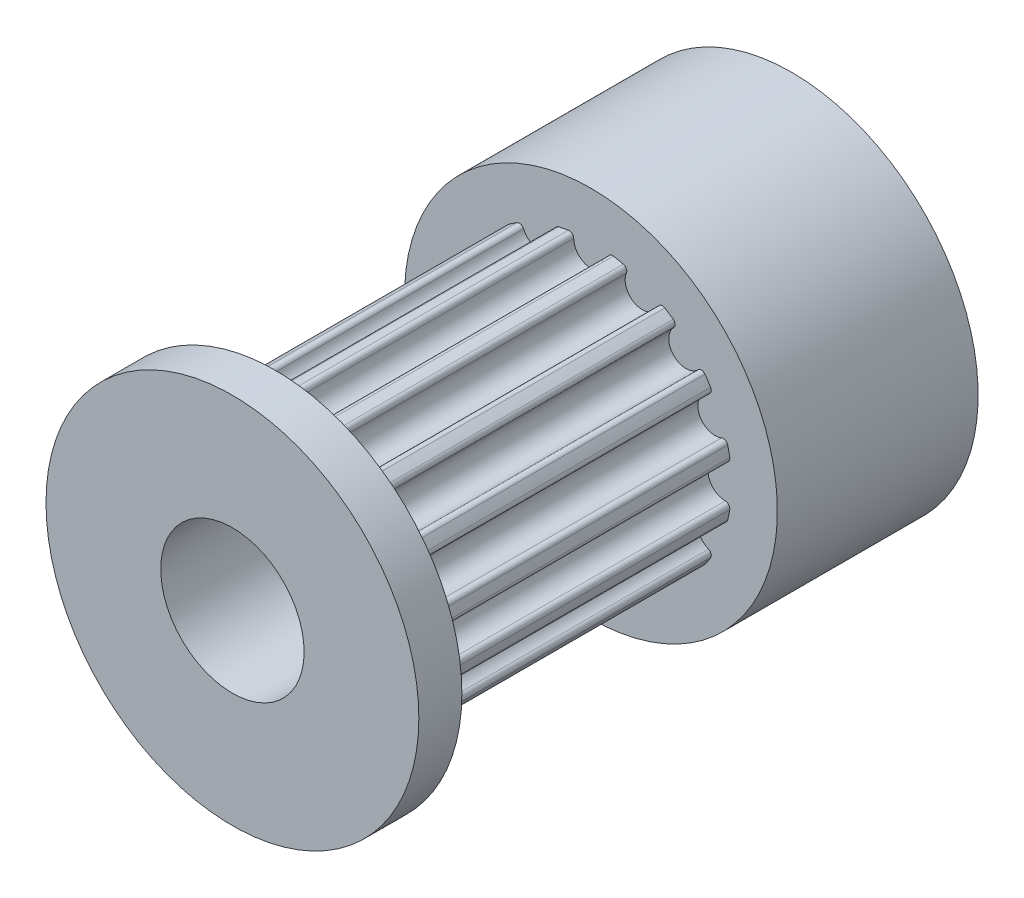
SolidWorks part; units mm, degrees
ref_plane "Спереди" through (0, 0, 0) normal (0, 0, 1) x (1, 0, 0)
ref_plane "Сверху" through (0, 0, 0) normal (0, 1, 0) x (1, 0, 0)
ref_plane "Справа" through (0, 0, 0) normal (1, 0, 0) x (0, 0, -1)
ref_axis "Ось1" through (0, 0, 55) along (0, 0, -1)
sketch "SketchRevolveGearBelt01" plane through (0, 0, 0) normal (1, 0, 0) x (0, 0, -1)
  line L1 (5.5, 0) -> (5.5, 4.9025)
  line L2 (5.5, 4.9025) -> (-5.5, 4.9025)
  line L3 (-5.5, 4.9025) -> (-5.5, 0)
  line L4 (-5.5, 0) -> (5.5, 0)
  dimension "D1" = 11
  dimension "D2" = 5.5
  dimension "D3" = 4.9025
revolve "GearBelt01" add sketch "SketchRevolveGearBelt01" angle 360 about L4 region at (0, 2.4512, 0)
sketch "SketchToothGearBelt01" plane through (0, 0, 0) normal (0, 0, 1) x (1, 0, 0)
  line L0 (-0.7833, 4.8395) -> (0, 7.4425)
  line L1 (0, 7.4425) -> (0.7833, 4.8395)
  arc A0 (0.7833, 4.8395) -> (0.6, 4.6835) centre (0.758, 4.6835) ccw
  arc A1 (0.6, 4.6835) -> (-0.6, 4.6835) centre (0, 4.6835) cw
  arc A2 (-0.6, 4.6835) -> (-0.7833, 4.8395) centre (-0.758, 4.6835) ccw
  dimension "GearBeltToothR1" = 0.3161
  dimension "GearBeltToothR2" = 1.2
  dimension "GearBeltToothCapX1" = 0.7833
  dimension "GearBeltToothCapY1" = 2.603
  dimension "GearBeltToothCapX2" = 0.7833
  dimension "GearBeltToothCapY2" = 2.603
extrude "ToothExtrudeCutGearBelt01" cut sketch "SketchToothGearBelt01" against normal blind 5.5 and the other way blind 5.5
ref_axis "Ось2" through (5.3927, 0, 0) along (-1, 0, 0)
ref_plane "Плоскость1" through (0, 0, 0) normal (0, 0, -1) x (1, 0, 0)
pattern_circular "PatternGearBelt01" count 16 every 22.5 about axis through (0, 0, 55) along (0, 0, -1) of "ToothExtrudeCutGearBelt01"
sketch "AuxiliarySketchGearBelt01" plane through (0, 0, 0) normal (0, 0, 1) x (1, 0, 0)
  circle A0 centre (0, 0) radius 5.093 construction
  dimension "PitchDiameter" = 10.1859
sketch "Эскиз5" plane through (0, 0, 5.5) normal (0, 0, 1) x (1, 0, 0)
  circle A0 centre (0, 0) radius 6.5
  dimension "D1" = 13
extrude "Бобышка-Вытянуть1" add sketch "Эскиз5" along normal blind 1.5
sketch "Эскиз6" plane through (0, 0, -5.5) normal (0, 0, -1) x (-1, 0, 0)
  circle A0 centre (0, 0) radius 6.5
  dimension "D1" = 13
extrude "Бобышка-Вытянуть2" add sketch "Эскиз6" along normal blind 7
sketch "Эскиз7" plane through (0, 0, 0) normal (0, 0, 1) x (1, 0, 0)
  circle A0 centre (0, 0) radius 2.5
extrude "Вырез-Вытянуть2" cut sketch "Эскиз7" against normal through all both and the other way through all
